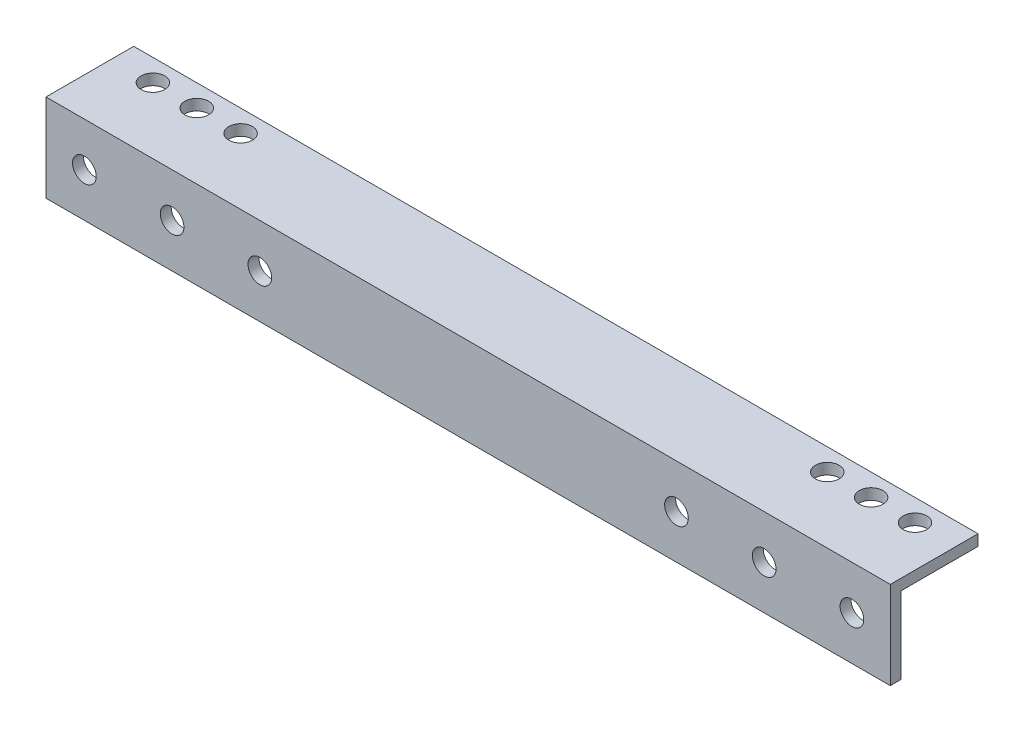
SolidWorks part; units mm, degrees
ref_plane "Front Plane" through (0, 0, 0) normal (0, 0, 1) x (1, 0, 0)
ref_plane "Top Plane" through (0, 0, 0) normal (0, 1, 0) x (1, 0, 0)
ref_plane "Right Plane" through (0, 0, 0) normal (1, 0, 0) x (0, 0, -1)
sketch "Sketch1" plane through (0, 0, 0) normal (1, 0, 0) x (0, 0, -1)
  line L0 (0, 0) -> (25.4, 0)
  line L2 (0, 0) -> (0, -25.4)
  line L4 (3.175, -3.175) -> (25.4, -3.175)
  line L5 (3.175, -3.175) -> (3.175, -25.4)
  line L6 (25.4, -3.175) -> (25.4, 0)
  line L7 (3.175, -25.4) -> (0, -25.4)
  line L8 (55, 0) -> (-55, 0) construction
  line L9 (0, 55) -> (0, -55) construction
  dimension "D1" = 25.4
  dimension "D2" = 25.4
  dimension "D4" = 3.175
  dimension "D3" = 3.175
extrude "Boss-Extrude1" add sketch "Sketch1" along normal blind 244.475
sketch "Sketch2" plane through (0, 0, 0) normal (0, 0, 1) x (1, 0, 0)
  line L0 (0, -12.7) -> (61.9125, -12.7) construction
  line L1 (0, -55) -> (0, 55) construction
  line L2 (244.475, -25.4) -> (0, -25.4) construction
  line L3 (0, 0) -> (0, -25.4) construction
  line L4 (122.2375, -25.4) -> (122.2375, 0) construction
  line L6 (244.475, 0) -> (0, 0) construction
  line L7 (244.475, -12.7) -> (182.5625, -12.7) construction
  circle A0 centre (11.1125, -12.7) radius 3.429
  circle A1 centre (36.5125, -12.7) radius 3.429
  circle A2 centre (61.9125, -12.7) radius 3.429
  circle A3 centre (182.5625, -12.7) radius 3.429
  circle A4 centre (207.9625, -12.7) radius 3.429
  circle A5 centre (233.3625, -12.7) radius 3.429
  dimension "D1" = 12.7
  dimension "D2" = 6.858
  dimension "D3" = 11.1125
  dimension "D5" = 25.4
  dimension "D4" = 3
extrude "Cut-Extrude1" cut sketch "Sketch2" against normal up to surface (3.175 mm away) up to face at (122.2375, -14.2875, -3.175)
sketch "Sketch3" plane through (0, 0, 0) normal (0, 1, 0) x (1, 0, 0)
  line L1 (0, -13.97) -> (0, 13.97) construction
  line L4 (122.2375, 25.4) -> (122.2375, 0) construction
  line L5 (244.475, 25.4) -> (0, 25.4) construction
  line L6 (244.475, 0) -> (0, 0) construction
  circle A0 centre (11.8999, 19.05) radius 3.429
  circle A1 centre (24.5999, 19.05) radius 3.429
  circle A2 centre (37.2999, 19.05) radius 3.429
  circle A3 centre (207.1751, 19.05) radius 3.429
  circle A4 centre (219.8751, 19.05) radius 3.429
  circle A5 centre (232.5751, 19.05) radius 3.429
  dimension "D1" = 6.858
  dimension "D2" = 11.8999
  dimension "D5" = 19.05
  dimension "D4" = 12.7
  dimension "D3" = 3
extrude "Cut-Extrude2" cut sketch "Sketch3" against normal up to surface (3.175 mm away) up to face at (122.2375, -3.175, -14.2875)
